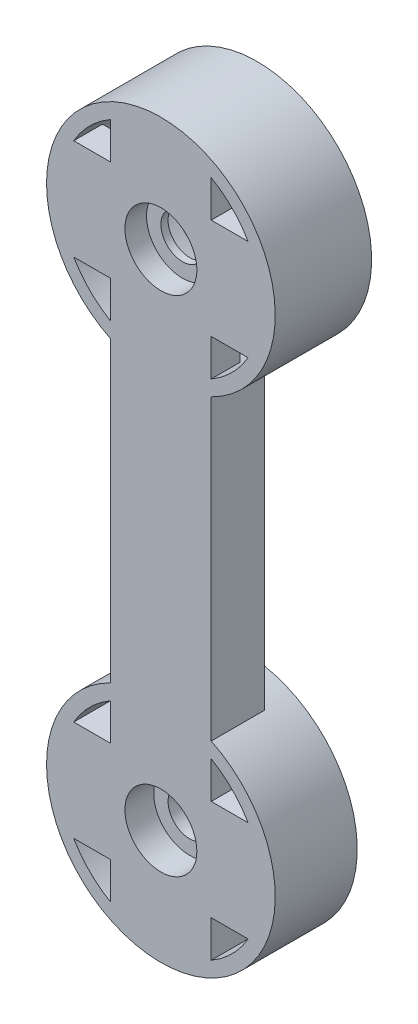
SolidWorks part; units mm, degrees
ref_plane "Front Plane" through (0, 0, 0) normal (0, 0, 1) x (1, 0, 0)
ref_plane "Top Plane" through (0, 0, 0) normal (0, 1, 0) x (1, 0, 0)
ref_plane "Right Plane" through (0, 0, 0) normal (1, 0, 0) x (0, 0, -1)
sketch "Sketch1" plane through (0, 0, 0) normal (0, 0, 1) x (1, 0, 0)
  line L5 (0, -17.5) -> (12.7696, -17.5) construction
  line L26 (0, 0) -> (0, -35) construction
  line L32 (0, 3.5) -> (7.1381, 3.5)
  line L33 (7.1381, 3.5) -> (-7.1381, 3.5)
  line L34 (0, -3.5) -> (7.1381, -3.5)
  line L35 (7.1381, -3.5) -> (-7.1381, -3.5)
  line L36 (3.5, -35) -> (3.5, -41.0622)
  line L37 (-3.5, -35) -> (-3.5, -41.0622)
  line L38 (-3.5, 0) -> (-3.5, 6.0622)
  line L45 (-3.5, 0) -> (-3.5, -35)
  line L47 (3.5, 0) -> (3.5, -35)
  line L48 (3.5, 0) -> (3.5, 6.0622)
  line L49 (7.1381, -31.5) -> (-7.1381, -31.5)
  line L50 (0, -31.5) -> (7.1381, -31.5)
  line L51 (7.1381, -38.5) -> (-7.1381, -38.5)
  line L52 (0, -38.5) -> (7.1381, -38.5)
  circle A0 centre (0, 0) radius 7.95
  circle A1 centre (0, 0) radius 3.5
  circle A2 centre (0, 0) radius 7
  circle A6 centre (0, 0) radius 1.5
  circle A11 centre (0, -35) radius 1.5
  circle A12 centre (0, -35) radius 7
  circle A13 centre (0, -35) radius 3.5
  circle A14 centre (0, -35) radius 7.95
  point P20 (0, -35)
  point P34 (0, -35)
  point P42 (0, 0)
  dimension "D1" = 15.9
  dimension "D2" = 7
  dimension "D6" = 14
  dimension "D9" = 3
  dimension "D3" = 7
  dimension "D7" = 35
extrude "Boss-Extrude4" add sketch "Sketch1" along normal blind 3 contours L48 A2 L38 L33 L32 | A2 L32 A0 L33 | L45 A14 L47 A0 | A14 L51 A12 | A12 L36 L51 L37 | A14 L49 A12 L51 | L36 A13 L51 | L51 A13 L37 | A14 L51 A12 L49 | A13 A11 | L45 A13 L49 | L49 A13 L47 | A12 L45 L49 L47 | A14 L49 A12 L45 | A14 L47 A12 L49 | A14 L45 A12 L47 | A12 L51 L37 L45 L49 | A12 L50 L47 L36 L52 | L45 A2 L47 L34 L35 | A2 L45 A0 L47 | A2 L47 A0 L34 | A2 L34 A0 L32 | A2 L33 A0 L35 | A2 L35 A0 L45 | L33 A2 L35 L45 L38 | L35 A2 L33 L48 L47 | A1 L34 L47 | A1 A6 | A1 L45 L35 | A1 L33 L38 | A1 L48 L32 region at (0, 5.1101, 0) region at (-2.7182, 2.7182, 0) region at (2.7182, 2.7182, 0) region at (2.4049, 2.4049, 0) region at (5.1101, 0, 0) region at (-5.1101, 0, 0) region at (2.7182, -2.7182, 0) region at (-2.7182, -2.7182, 0) region at (5.0555, 5.0555, 0) region at (7.1812, 0, 0) region at (-7.1812, 0, 0) region at (0, -5.1101, 0) region at (-5.2259, -5.2259, 0) region at (5.2259, -5.2259, 0) region at (0, -7.1812, 0) region at (0, -17.5, 0) region at (5.2259, -29.7741, 0) region at (0, -27.8188, 0) region at (-5.2259, -29.7741, 0) region at (0, -29.8899, 0) region at (7.1812, -35, 0) region at (-7.1812, -35, 0) region at (5.1101, -35, 0) region at (2.7182, -32.2818, 0) region at (-2.7182, -32.2818, 0) region at (-5.1101, -35, 0) region at (-6.6001, -38.6495, 0) region at (2.4049, -37.4049, 0) region at (2.7182, -37.7182, 0) region at (-2.7182, -37.7182, 0) region at (0, -40.1101, 0)
sketch "Sketch3" plane through (0, 0, 0) normal (0, 0, -1) x (-1, 0, 0)
  line L0 (-3.5, 6.0622) -> (-3.5, 3.5)
  line L1 (-3.5, 3.5) -> (-6.0622, 3.5)
  line L2 (-3.5, -6.0622) -> (-3.5, -3.5)
  line L3 (-3.5, -3.5) -> (-6.0622, -3.5)
  line L4 (3.5, -6.0622) -> (3.5, -3.5)
  line L5 (3.5, -3.5) -> (6.0622, -3.5)
  line L6 (3.5, 6.0622) -> (3.5, 3.5)
  line L7 (3.5, 3.5) -> (6.0622, 3.5)
  line L8 (0, 0) -> (0, -35) construction
  line L9 (0, -35) -> (0, -17.5) construction
  line L10 (0, -17.5) -> (14.5774, -17.5) construction
  line L11 (-3.5, 3.5) -> (-6.0622, 3.5)
  line L12 (-3.5, 6.0622) -> (-3.5, 3.5)
  line L13 (-3.5, -3.5) -> (-6.0622, -3.5)
  line L14 (-3.5, -6.0622) -> (-3.5, -3.5)
  line L15 (3.5, -3.5) -> (6.0622, -3.5)
  line L16 (3.5, -6.0622) -> (3.5, -3.5)
  line L17 (3.5, 3.5) -> (6.0622, 3.5)
  line L18 (3.5, 6.0622) -> (3.5, 3.5)
  line L19 (3.5, -41.0622) -> (3.5, -38.5)
  line L20 (3.5, -38.5) -> (6.0622, -38.5)
  line L21 (3.5, -28.9378) -> (3.5, -31.5)
  line L22 (3.5, -31.5) -> (6.0622, -31.5)
  line L23 (-3.5, -28.9378) -> (-3.5, -31.5)
  line L24 (-3.5, -31.5) -> (-6.0622, -31.5)
  line L25 (-3.5, -41.0622) -> (-3.5, -38.5)
  line L26 (-3.5, -38.5) -> (-6.0622, -38.5)
  line L27 (3.5, -38.5) -> (6.0622, -38.5)
  line L28 (3.5, -41.0622) -> (3.5, -38.5)
  line L29 (3.5, -31.5) -> (6.0622, -31.5)
  line L30 (3.5, -28.9378) -> (3.5, -31.5)
  line L31 (-3.5, -31.5) -> (-6.0622, -31.5)
  line L32 (-3.5, -28.9378) -> (-3.5, -31.5)
  line L33 (-3.5, -38.5) -> (-6.0622, -38.5)
  line L34 (-3.5, -41.0622) -> (-3.5, -38.5)
  circle A0 centre (0, 0) radius 1.5
  circle A1 centre (0, 0) radius 7.95
  circle A2 centre (0, 0) radius 7
  circle A3 centre (0, -35) radius 7
  circle A4 centre (0, -35) radius 7.95
  circle A5 centre (0, -35) radius 1.5
  line M2 (3.5, -38.5) -> (6.0622, -38.5)
  arc M3 (6.0622, -38.5) -> (3.5, -41.0622) centre (0, -35) cw
  line M4 (3.5, -41.0622) -> (3.5, -38.5)
  line M5 (-3.5, -38.5) -> (-3.5, -41.0622)
  arc M6 (-3.5, -41.0622) -> (-6.0622, -38.5) centre (0, -35) cw
  line M7 (-6.0622, -38.5) -> (-3.5, -38.5)
  arc M9 (3.5, -7.1381) -> (-3.5, -7.1381) centre (0, 0) ccw
  arc M11 (-3.5, -27.8619) -> (3.5, -27.8619) centre (0, -35) ccw
  line M12 (6.0622, -31.5) -> (3.5, -31.5)
  line M13 (3.5, -31.5) -> (3.5, -28.9378)
  arc M14 (3.5, -28.9378) -> (6.0622, -31.5) centre (0, -35) cw
  arc M15 (-3.5, -6.0622) -> (-6.0622, -3.5) centre (0, 0) cw
  line M16 (-6.0622, -3.5) -> (-3.5, -3.5)
  line M17 (-3.5, -3.5) -> (-3.5, -6.0622)
  line M18 (-3.5, -31.5) -> (-6.0622, -31.5)
  arc M19 (-6.0622, -31.5) -> (-3.5, -28.9378) centre (0, -35) cw
  line M20 (-3.5, -28.9378) -> (-3.5, -31.5)
  line M21 (3.5, -3.5) -> (6.0622, -3.5)
  arc M22 (6.0622, -3.5) -> (3.5, -6.0622) centre (0, 0) cw
  line M23 (3.5, -6.0622) -> (3.5, -3.5)
  line M24 (6.0622, 3.5) -> (3.5, 3.5)
  line M25 (3.5, 3.5) -> (3.5, 6.0622)
  arc M26 (3.5, 6.0622) -> (6.0622, 3.5) centre (0, 0) cw
  arc M27 (-6.0622, 3.5) -> (-3.5, 6.0622) centre (0, 0) cw
  line M28 (-3.5, 6.0622) -> (-3.5, 3.5)
  line M29 (-3.5, 3.5) -> (-6.0622, 3.5)
  circle M30 centre (0, 0) radius 1.5
  circle M31 centre (0, -35) radius 1.5
  dimension "D1" = 15.9
extrude "Boss-Extrude5" add sketch "Sketch3" along normal blind 3 contours A1 A2 M9 M26 M22 M15 M27 | A2 M25 M28 M29 M16 M17 M23 M21 M24 M30 | A3 M4 M2 M12 M13 M20 M18 M7 M5 M31 | A4 A3 M11 M3 M6 M19 M14 region at (0, 6.802, 0) region at (0, -41.802, 0) region at (-6.5556, -4.0868, 0) region at (4.0868, -41.5556, 0)
sketch "Sketch4" plane through (0, 0, 3) normal (0, 0, 1) x (1, 0, 0)
  line L0 (0, 0) -> (0, -35) construction
  line L1 (0, -35) -> (0, 0) construction
  line L2 (0, -17.5) -> (19.6941, -17.5) construction
  circle A1 centre (0, -35) radius 2.5
  circle A2 centre (0, 0) radius 2.5
  dimension "D2" = 5
extrude "Cut-Extrude1" cut sketch "Sketch4" against normal blind 1.5
sketch "Sketch5" plane through (0, 0, -3) normal (0, 0, -1) x (-1, 0, 0)
  circle A0 centre (0, 0) radius 7
extrude "Cut-Extrude2" cut sketch "Sketch5" against normal blind 4
sketch "Sketch6" plane through (0, 0, -3) normal (0, 0, -1) x (-1, 0, 0)
  circle A0 centre (0, -35) radius 7.95
extrude "Cut-Extrude3" cut sketch "Sketch6" against normal blind 1
sketch "Sketch7" plane through (0, 0, 1.5) normal (0, 0, 1) x (1, 0, 0)
  circle A0 centre (0, -35) radius 2.5
extrude "Cut-Extrude4" cut sketch "Sketch7" against normal blind 0.5
sketch "Sketch8" plane through (0, 0, -3) normal (0, 0, -1) x (-1, 0, 0)
  circle A0 centre (0, 0) radius 7.95
  circle A1 centre (0, 0) radius 7
extrude "Boss-Extrude6" add sketch "Sketch8" along normal blind 0.7
sketch "Sketch9" plane through (0, 0, -2) normal (0, 0, -1) x (-1, 0, 0)
  line L0 (-3.5, -28.9378) -> (-3.5, -31.5)
  line L1 (-3.5, -31.5) -> (-6.0622, -31.5)
  line L2 (-6.0622, -38.5) -> (-3.5, -38.5)
  line L3 (-3.5, -38.5) -> (-3.5, -41.0622)
  line L4 (6.0622, -38.5) -> (3.5, -38.5)
  line L5 (3.5, -38.5) -> (3.5, -41.0622)
  line L6 (3.5, -28.9378) -> (3.5, -31.5)
  line L7 (3.5, -31.5) -> (6.0622, -31.5)
  circle A0 centre (0, -35) radius 7.95
  circle A1 centre (0, -35) radius 7
  circle A2 centre (0, -35) radius 1.5
  line M1 (6.0622, -31.5) -> (3.5, -31.5)
  line M2 (3.5, -31.5) -> (3.5, -28.9378)
  arc M3 (3.5, -28.9378) -> (6.0622, -31.5) centre (0, -35) cw
  arc M4 (-3.5, -41.0622) -> (-6.0622, -38.5) centre (0, -35) cw
  line M5 (-6.0622, -38.5) -> (-3.5, -38.5)
  line M6 (-3.5, -38.5) -> (-3.5, -41.0622)
  arc M7 (6.0622, -38.5) -> (3.5, -41.0622) centre (0, -35) cw
  line M8 (3.5, -41.0622) -> (3.5, -38.5)
  line M9 (3.5, -38.5) -> (6.0622, -38.5)
  circle M10 centre (0, -35) radius 7.95
  line M11 (-3.5, -31.5) -> (-6.0622, -31.5)
  arc M12 (-6.0622, -31.5) -> (-3.5, -28.9378) centre (0, -35) cw
  line M13 (-3.5, -28.9378) -> (-3.5, -31.5)
  circle M14 centre (0, -35) radius 1.5
extrude "Boss-Extrude8" add sketch "Sketch9" along normal blind 0.7 contours A1 M2 M13 M11 M5 M6 M8 M9 M1 M14 | A1 M10 M3 M7 M4 M12 region at (0, -28.198, -2) region at (7.7251, -35, -2)
sketch "Sketch10" plane through (0, 0, 0) normal (0, 0, -1) x (-1, 0, 0)
  line L2 (-3.5, -7.1381) -> (-3.5, -27.8619)
  line L4 (3.5, -7.1381) -> (3.5, -27.8619)
  circle A0 centre (0, 0) radius 7.95
  circle A1 centre (0, -35) radius 7.95
  line M1 (-3.5, -7.1381) -> (-3.5, -27.8619)
  arc M2 (-3.5, -27.8619) -> (3.5, -27.8619) centre (0, -35) cw
  line M3 (3.5, -27.8619) -> (3.5, -7.1381)
  arc M4 (3.5, -7.1381) -> (-3.5, -7.1381) centre (0, 0) cw
extrude "Boss-Extrude9" add sketch "Sketch10" along normal blind 0.7 contours M4 M1 M2 M3 region at (0, -17.5, 0)
